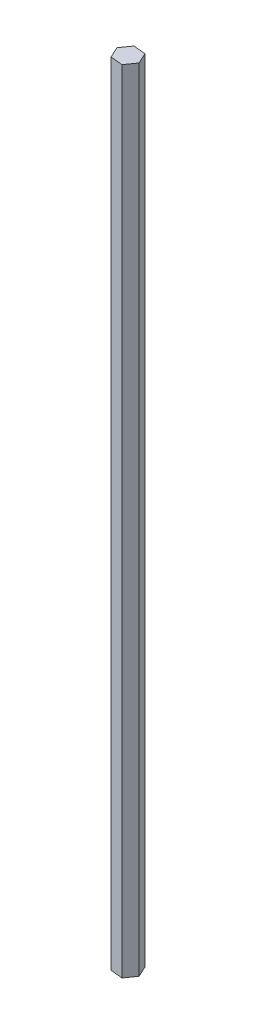
SolidWorks part; units mm, degrees
ref_plane "Front Plane" through (0, 0, 0) normal (0, 0, 1) x (1, 0, 0)
ref_plane "Top Plane" through (0, 0, 0) normal (0, 1, 0) x (1, 0, 0)
ref_plane "Right Plane" through (0, 0, 0) normal (1, 0, 0) x (0, 0, -1)
sketch "Sketch1" plane through (0, 0, 0) normal (0, 1, 0) x (1, 0, 0)
  line L1 (3.0585, -6.664) -> (7.3004, -0.6833)
  line L2 (7.3004, -0.6833) -> (4.242, 5.9807)
  line L3 (4.242, 5.9807) -> (-3.0585, 6.664)
  line L4 (-3.0585, 6.664) -> (-7.3004, 0.6833)
  line L5 (-7.3004, 0.6833) -> (-4.242, -5.9807)
  line L6 (-4.242, -5.9807) -> (3.0585, -6.664)
  circle A0 centre (0, 0) radius 6.35 construction
  dimension "D1" = 12.7
extrude "Boss-Extrude1" add sketch "Sketch1" along normal blind 476.25
ref_axis "Axis1" through (0, 694.6405, 0) along (0, -1, 0)
